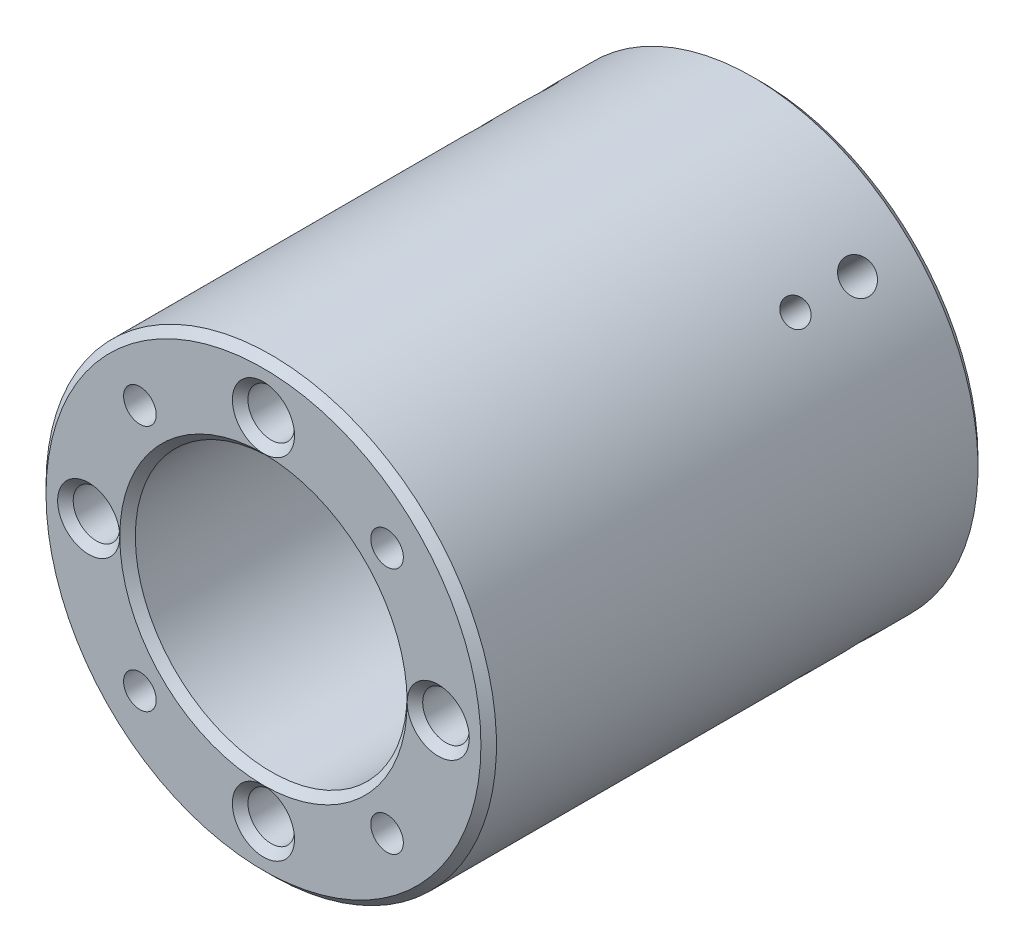
SolidWorks part; units mm, degrees
material "7050-T73510"
ref_plane "前视基准面" through (0, 0, 0) normal (0, 0, 1) x (1, 0, 0)
ref_plane "上视基准面" through (0, 0, 0) normal (0, 1, 0) x (1, 0, 0)
ref_plane "右视基准面" through (0, 0, 0) normal (1, 0, 0) x (0, 0, -1)
sketch "草图1" plane through (0, 0, 0) normal (1, 0, 0) x (0, 0, -1)
  line L0 (-74.6009, 0) -> (91.0329, 0) construction
  line L1 (0, 17.5) -> (40, 17.5)
  line L2 (40, 17.5) -> (40, 10)
  line L3 (40, 10) -> (64, 10)
  line L4 (0, 29) -> (64, 29)
  line L5 (0, 29) -> (0, 17.5)
  line L6 (64, 29) -> (64, 10)
  line L7 (0, 36.0374) -> (0, -10.1247) construction
  dimension "D1" = 35
  dimension "D2" = 40
  dimension "D3" = 20
  dimension "D4" = 58
  dimension "D5" = 24
  dimension "D6" = 64
revolve "旋转1" add sketch "草图1" angle 360 about L0 region at (0, 21.3832, -35.9301)
sketch "草图2" plane through (0, 0, 0) normal (0, 0, 1) x (1, 0, 0)
  line L0 (0, 31.2509) -> (0, -33.7203) construction
  line L1 (-39.5528, 0) -> (57.0461, 0) construction
  line L2 (-27.0864, 27.0864) -> (0, 0) construction
  line L3 (0, 0) -> (32.2866, -32.2866) construction
  circle A5 centre (22.5, 0) radius 3
  circle A6 centre (-22.5, 0) radius 3
  circle A7 centre (0, -22.5) radius 3
  circle A8 centre (0, 22.5) radius 3
  point P18 (-15.9099, 15.9099)
  point P20 (15.9099, 15.9099)
  point P22 (15.9099, -15.9099)
  point P23 (-15.9099, -15.9099)
  dimension "D2" = 22.5
  dimension "D3" = 6
  dimension "D1" = 45
sketch "草图3" plane through (0, 0, 0) normal (0, 0, 1) x (1, 0, 0)
  line L0 (-35.3405, 0) -> (40.481, 0) construction
  line L1 (0, 31.5728) -> (0, -36.7825) construction
  line L2 (0, 0) -> (15.9099, 15.9099) construction
  dimension "D1" = 22.5
  dimension "D2" = 45
hole_wizard "M5 螺纹孔1" positions "草图4" profile "草图5" tap size "M5" standard "GB"
sketch "草图4" plane through (0, 0, 0) normal (0, 0, 1) x (1, 0, 0)
  point P0 (15.9099, 15.9099)
cosmetic thread "装饰螺纹线1" parameters "D1"=10, "D2"=5
sketch "草图5" plane through (15.9099, 15.9099, 0) normal (1, 0, 0) x (0, -1, 0)
  line L0 (0, 0) -> (0, 15.2618)
  line L1 (0, 15.2618) -> (2.1, 14)
  line L2 (2.1, 14) -> (2.1, 0)
  line L5 (2.1, 0) -> (0, 0)
  line L10 (0, 15.2618) -> (-2.1, 14) construction
  line L11 (0, -6.35) -> (0, 107.95) construction
  dimension "螺纹孔钻头直径" = 4.2
  dimension "螺纹孔钻头深度" = 14
  dimension "导头角度" = 118
cosmetic thread "孔螺蚊线4" parameters "D1"=10, "D2"=5.2
pattern_circular "阵列(圆周)1" count 4 over 360 about axis through (0, 0, 0) along (0, 0, 1) of "M5 螺纹孔1"
cosmetic thread "装饰螺纹线4" parameters "D1"=5, "D2"=5
cosmetic thread "装饰螺纹线5" parameters "D1"=5, "D2"=5
cosmetic thread "装饰螺纹线6" parameters "D1"=5, "D2"=5
chamfer "倒角1" distance 1 angle 45 2 edges at (29, 0, -64) (29, 0, 0)
chamfer "倒角2" distance 1 angle 45 3 edges at (10, 0, -64) (17.5, 0, 0) (10, 0, -40)
ref_plane "基准面4" through (0, 0, 0) normal (0.7071, -0.7071, 0) x (0.7071, 0.7071, 0)
sketch "草图10" plane through (0, 0, 0) normal (0.7071, -0.7071, 0) x (0.7071, 0.7071, 0)
  line L0 (0, 17.4058) -> (0, -78.3963) construction
  line L1 (28, -64) -> (-28, -64) construction
  point P3 (0, -56)
  point P4 (0, -48)
  dimension "D1" = 8
  dimension "D2" = 8
hole_wizard "大小mm 暗销孔1" positions "草图15" profile "草图17" hole size "Ø6.0" standard "GB"
sketch "草图15" plane through (0, 0, 0) normal (0, 0, 1) x (1, 0, 0)
  point P0 (0, -22.5)
  point P3 (-22.5, 0)
  point P6 (0, 22.5)
  point P9 (22.5, 0)
sketch "草图17" plane through (0, -22.5, 0) normal (1, 0, 0) x (0, -1, 0)
  line L0 (0, 0) -> (0, 7.8026)
  line L1 (0, 7.8026) -> (3, 6)
  line L2 (3, 6) -> (3, 0)
  line L5 (3, 0) -> (0, 0)
  line L10 (0, 7.8026) -> (-3, 6) construction
  line L11 (0, -6.35) -> (0, 107.95) construction
  dimension "孔直径" = 6
  dimension "孔深度" = 6
  dimension "导头角度" = 118
hole_wizard "M4 螺纹孔1" positions "草图19" profile "草图18" tap size "M4" standard "GB" end condition through all
sketch "草图19" plane through (0, 0, 0) normal (0.7071, -0.7071, 0) x (0.7071, 0.7071, 0)
  point P0 (0, -48)
sketch "草图18" plane through (0, 0, -48) normal (0.5774, 0.5774, 0.5774) x (-0.4082, -0.4082, 0.8165)
  line L0 (0, 0) -> (0, 41.0122)
  line L1 (0, 41.0122) -> (1.65, 41.0122)
  line L2 (1.65, 41.0122) -> (1.65, 0)
  line L5 (1.65, 0) -> (0, 0)
  line L11 (0, -6.35) -> (0, 107.95) construction
  dimension "通孔螺纹孔钻头直径" = 3.3
  dimension "通孔螺纹孔钻头深度" = 41.0122
cosmetic thread "孔螺蚊线5" parameters "D2"=4
hole_wizard "M5 螺纹孔3" positions "草图25" profile "草图24" tap size "M5" standard "GB" end condition through all
sketch "草图25" plane through (0, 0, 0) normal (0.7071, -0.7071, 0) x (0.7071, 0.7071, 0)
  point P0 (0, -56)
sketch "草图24" plane through (0, 0, -56) normal (0.5774, 0.5774, 0.5774) x (-0.4082, -0.4082, 0.8165)
  line L0 (0, 0) -> (0, 41.0122)
  line L1 (0, 41.0122) -> (2.1, 41.0122)
  line L2 (2.1, 41.0122) -> (2.1, 0)
  line L5 (2.1, 0) -> (0, 0)
  line L11 (0, -6.35) -> (0, 107.95) construction
  dimension "通孔螺纹孔钻头直径" = 4.2
  dimension "通孔螺纹孔钻头深度" = 41.0122
cosmetic thread "孔螺蚊线6" parameters "D2"=5
pattern_circular "阵列(圆周)2" count 4 every 90 about axis through (0, 0, -1) along (0, 0, -1) of "M4 螺纹孔1", "M5 螺纹孔3"
chamfer "倒角3" distance 1 angle 45 4 edges at (25.5, 0, 0) (3, 22.5, 0) (3, -22.5, 0) (-19.5, 0, 0)
